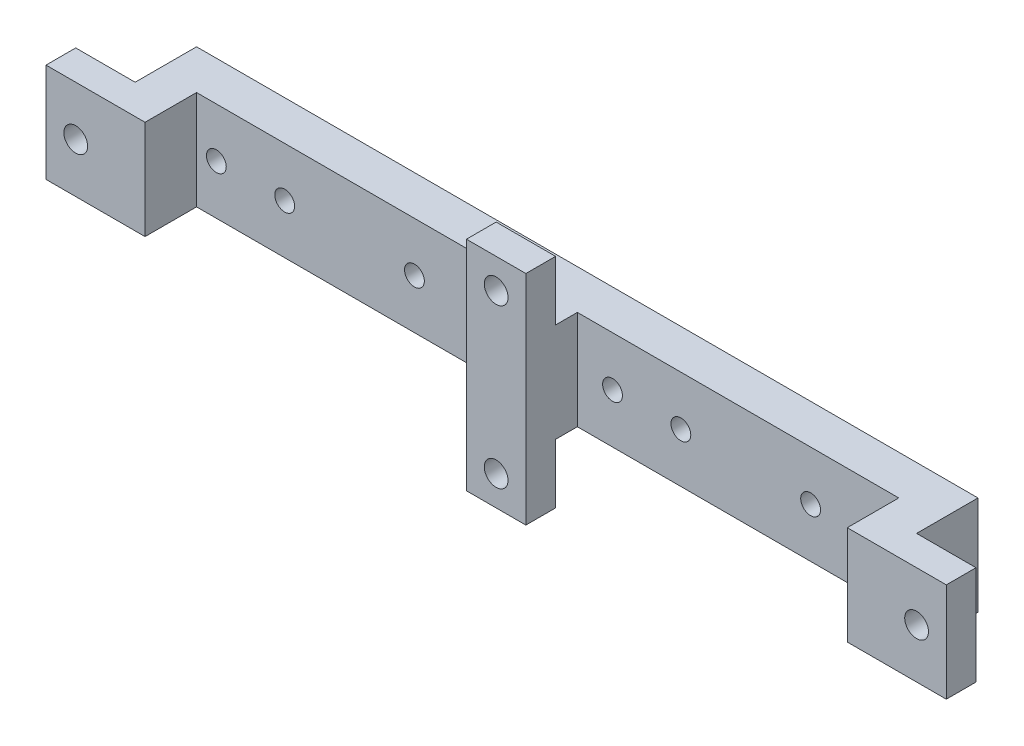
SolidWorks part; units mm, degrees
ref_plane "前视基准面" through (0, 0, 0) normal (0, 0, 1) x (1, 0, 0)
ref_plane "上视基准面" through (0, 0, 0) normal (0, 1, 0) x (1, 0, 0)
ref_plane "右视基准面" through (0, 0, 0) normal (1, 0, 0) x (0, 0, -1)
other "Configuration Table"
sketch "草图1" plane through (0, 0, 0) normal (0, 0, 1) x (1, 0, 0)
  line L0 (-16.725, 0) -> (-13.275, 0)
  line L9 (-17.725, 2.5) -> (17.725, 2.5)
  line L10 (-17.725, 2.5) -> (-17.725, -2.5)
  line L11 (-17.725, -2.5) -> (17.725, -2.5)
  line L12 (17.725, 2.5) -> (17.725, -2.5)
  line L13 (-6.725, 0) -> (-3.275, 0)
  line L14 (3.275, 0) -> (6.725, 0)
  line L15 (13.275, 0) -> (16.725, 0)
  line L16 (16.725, 0) -> (17.725, 0)
  line L17 (-16.725, 0) -> (-17.725, 0)
  line L18 (-15, 0) -> (-5, 0)
  line L19 (-5, 0) -> (5, 0)
  line L20 (5, 0) -> (15, 0)
  line L22 (17.725, 2.5) -> (19.725, 2.5)
  line L23 (17.725, 2.5) -> (17.725, -2.5)
  line L24 (17.725, -2.5) -> (19.725, -2.5)
  line L25 (19.725, 2.5) -> (19.725, -2.5)
  line L26 (-17.725, 2.5) -> (-19.725, 2.5)
  line L27 (-17.725, 2.5) -> (-17.725, -2.5)
  line L28 (-17.725, -2.5) -> (-19.725, -2.5)
  line L29 (-19.725, 2.5) -> (-19.725, -2.5)
  line L30 (-1.5, 5.5) -> (1.5, 5.5)
  line L31 (-1.5, 5.5) -> (-1.5, -5.5)
  line L32 (-1.5, -5.5) -> (1.5, -5.5)
  line L33 (1.5, 5.5) -> (1.5, -5.5)
  line L34 (-19.725, 2.5) -> (-22.725, 2.5)
  line L35 (-19.725, 2.5) -> (-19.725, -2.5)
  line L36 (-19.725, -2.5) -> (-22.725, -2.5)
  line L37 (-22.725, 2.5) -> (-22.725, -2.5)
  line L38 (19.725, 2.5) -> (22.725, 2.5)
  line L39 (19.725, 2.5) -> (19.725, -2.5)
  line L40 (19.725, -2.5) -> (22.725, -2.5)
  line L41 (22.725, 2.5) -> (22.725, -2.5)
  circle A0 centre (-16.725, 0) radius 0.5
  circle A1 centre (-13.275, 0) radius 0.5
  circle A2 centre (-6.725, 0) radius 0.5
  circle A3 centre (-3.275, 0) radius 0.5
  circle A4 centre (3.275, 0) radius 0.5
  circle A5 centre (6.725, 0) radius 0.5
  circle A6 centre (13.275, 0) radius 0.5
  circle A7 centre (16.725, 0) radius 0.5
  circle A8 centre (-21.225, 0) radius 0.6
  circle A9 centre (0, 4) radius 0.6
  circle A10 centre (0, -4) radius 0.6
  circle A11 centre (21.225, 0) radius 0.6
  point P4 (0, 2.5)
  point P6 (-17.725, 0)
  point P37 (-1.5, 0)
  point P39 (0, -5.5)
  point P52 (0, 0)
  point P53 (0, 0)
  point P54 (-21.225, 2.5)
  point P55 (0, 0)
  point P56 (21.225, 2.5)
  dimension "D4" = 1
  dimension "D1" = 5
  dimension "D2" = 10
  dimension "D3" = 1
  dimension "D10" = 1.2
  dimension "D5" = 3.45
  dimension "D6" = 2
  dimension "D7" = 3
  dimension "D8" = 3
  dimension "D9" = 3
  dimension "D11" = 1.5
  dimension "D12" = 1.5
extrude "凸台-拉伸1" add sketch "草图1" along normal blind 2 contours L11 L12 L9 L10
extrude "切除-拉伸1" cut sketch "草图1<9>" along normal through all contours A0 | A1 | A2 | A3 | A4 | A5 | A6 | A7
sketch "草图1<9>" plane through (0, 0, 0) normal (0, 0, 1) x (1, 0, 0) same geometry as "草图1"
extrude "凸台-拉伸2" add sketch "草图1<10>" along normal blind 4.6 contours L26 L29 L28 L10 | L25 L22 L12 L24 | L33 L9 L31 L19 | L33 L19 L31 L11 region at (-18.725, 0, 0) region at (0, 1.25, 0) region at (0, -1.25, 0) region at (18.725, 0, 0)
sketch "草图1<10>" plane through (0, 0, 0) normal (0, 0, 1) x (1, 0, 0) same geometry as "草图1"
extrude "凸台-拉伸3" add sketch "草图1<12>" against normal blind 1.5 from surface contours L34 L37 L36 L29 | L33 L30 L31 L9 | L33 L11 L31 L32 | L41 L38 L25 L40 region at (-1.4576, 4, 0) region at (-19.7833, 0, 0) region at (0, -2.5424, 0) region at (21.225, 2.4417, 0) starting at face at (-18.725, 0, 4.6)
sketch "草图1<12>" plane through (0, 0, 0) normal (0, 0, 1) x (1, 0, 0) same geometry as "草图1"
